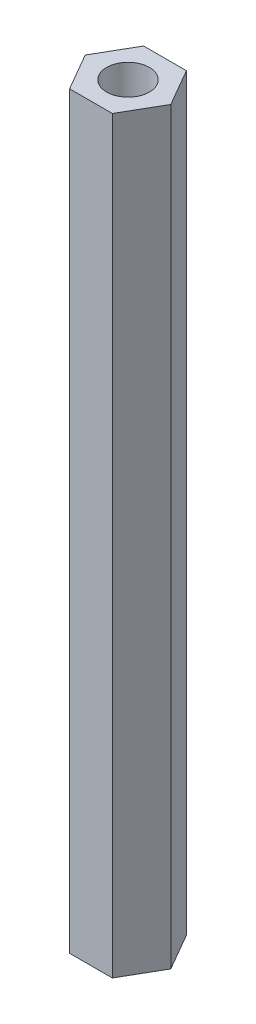
SolidWorks part; units mm, degrees
ref_plane "前视基准面" through (0, 0, 0) normal (0, 0, 1) x (1, 0, 0)
ref_plane "上视基准面" through (0, 0, 0) normal (0, 1, 0) x (1, 0, 0)
ref_plane "右视基准面" through (0, 0, 0) normal (1, 0, 0) x (0, 0, -1)
sketch "草图1" plane through (0, 0, 0) normal (0, 1, 0) x (1, 0, 0)
  line L0 (-1.9018, 4.3296) -> (2.0982, 4.3296)
  line L1 (2.0982, 4.3296) -> (4.0982, 0.8655)
  line L2 (4.0982, 0.8655) -> (2.0982, -2.5986)
  line L3 (2.0982, -2.5986) -> (-1.9018, -2.5986)
  line L4 (-1.9018, -2.5986) -> (-3.9018, 0.8655)
  line L5 (-3.9018, 0.8655) -> (-1.9018, 4.3296)
  line L6 (-3.9018, 0.8655) -> (4.0982, 0.8655)
  line L7 (-1.9018, 4.3296) -> (2.0982, -2.5986)
  circle A1 centre (0.0982, 0.8655) radius 2
  dimension "D5" = 4
  dimension "D1" = 120
  dimension "D2" = 120
  dimension "D3" = 120
  dimension "D4" = 120
  dimension "D6" = 4
  dimension "D7" = 4
  dimension "D8" = 4
  dimension "D9" = 4
extrude "凸台-拉伸1" add sketch "草图1" along normal blind 70 contours A1 L6 L1 L0 L7 | A1 L7 L5 L6 | A1 L6 L4 L3 L7 | A1 L7 L2 L6 region at (-2.2906, 0, -2.2446) region at (1.2926, 0, -2.9342) region at (-1.0962, 0, 1.2033) region at (2.487, 0, 0.5137)
